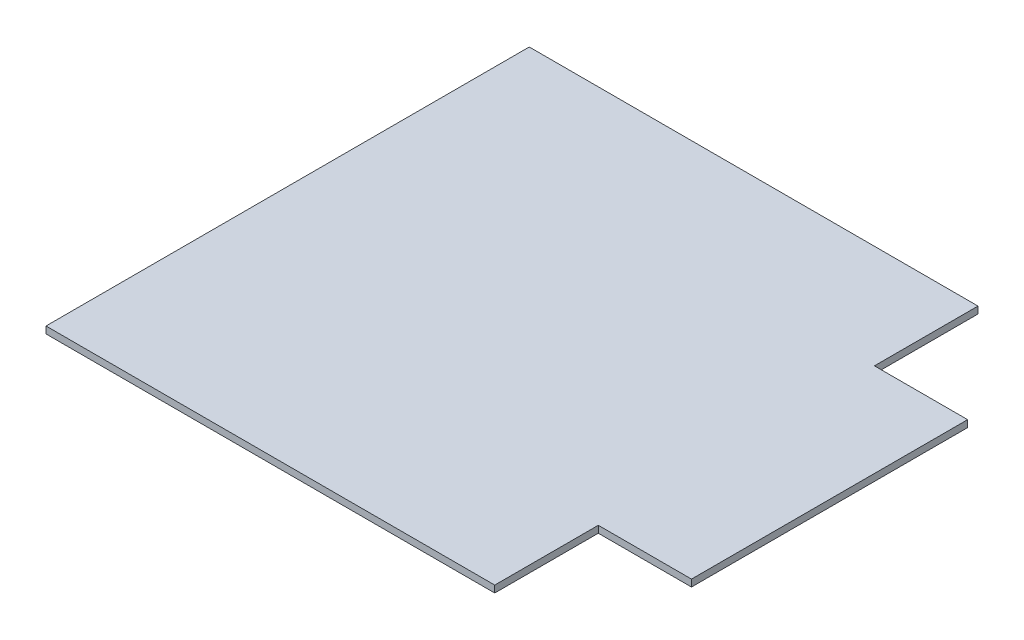
SolidWorks part; units mm, degrees
ref_plane "Front Plane" through (0, 0, 0) normal (0, 0, 1) x (1, 0, 0)
ref_plane "Top Plane" through (0, 0, 0) normal (0, 1, 0) x (1, 0, 0)
ref_plane "Right Plane" through (0, 0, 0) normal (1, 0, 0) x (0, 0, -1)
sketch "Sketch1" plane through (0, 0, 0) normal (0, 1, 0) x (1, 0, 0)
  line L0 (2.7953, 60.4757) -> (2.7953, -79.5243)
  line L1 (2.7953, -79.5243) -> (132.7953, -79.5243)
  line L2 (132.7953, -79.5243) -> (132.7953, -49.5243)
  line L3 (132.7953, -49.5243) -> (159.7953, -49.5243)
  line L4 (159.7953, -49.5243) -> (159.7953, 30.4757)
  line L5 (159.7953, 30.4757) -> (132.7953, 30.4757)
  line L6 (132.7953, 30.4757) -> (132.7953, 60.4757)
  line L7 (132.7953, 60.4757) -> (2.7953, 60.4757)
  point P9 (0, 0)
  dimension "D1" = 80
  dimension "D2" = 30
  dimension "D3" = 30
  dimension "D4" = 130
  dimension "D6" = 27
  dimension "D7" = 27
extrude "Boss-Extrude1" add sketch "Sketch1" along normal blind 2
